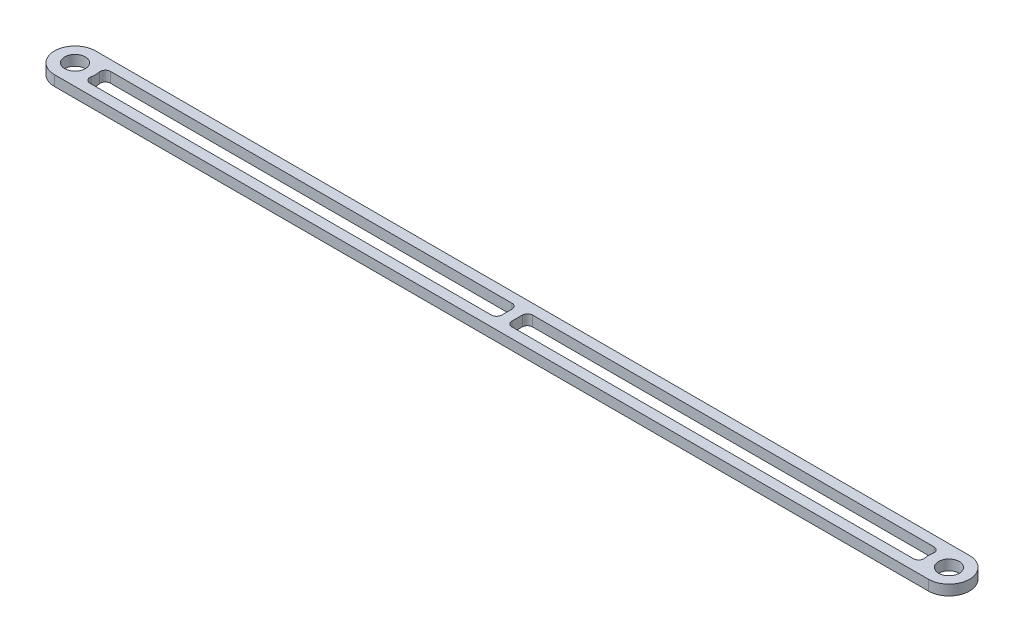
SolidWorks part; units mm, degrees
ref_plane "Front Plane" through (0, 0, 0) normal (0, 0, 1) x (1, 0, 0)
ref_plane "Top Plane" through (0, 0, 0) normal (0, 1, 0) x (1, 0, 0)
ref_plane "Right Plane" through (0, 0, 0) normal (1, 0, 0) x (0, 0, -1)
sketch "Sketch1" plane through (0, 0, 0) normal (0, 1, 0) x (1, 0, 0)
  line L0 (170, 0) -> (0, 0) construction
  line L1 (0, 4) -> (170, 4)
  line L2 (0, -4) -> (170, -4)
  line L3 (0, 2) -> (170, 2)
  line L4 (170, -2) -> (0, -2)
  line L5 (85, 2) -> (85, -2) construction
  line L6 (84, 2) -> (84, -2)
  line L7 (86, 2) -> (86, -2)
  circle A0 centre (0, 0) radius 2
  circle A1 centre (170, 0) radius 2
  circle A2 centre (0, 0) radius 4
  circle A3 centre (170, 0) radius 4
  dimension "D1" = 4
  dimension "D2" = 4
  dimension "D4" = 2
  dimension "D5" = 2
  dimension "D6" = 1
  dimension "D3" = 170
  dimension "D7" = 2
extrude "Boss-Extrude1" add sketch "Sketch1" along normal blind 2 contours A2 L4 A0 L3 | L4 A2 L3 A0 | A3 L4 A2 L2 | A3 L1 A2 L3 | L7 L3 L6 L4 | A3 L3 A1 L4 | L3 A3 L4 A1 region at (1.9453, 0, -3.3693) region at (85, 0, -3.0054) region at (172.7511, 0, -2.7511) region at (85, 0, 3.0054) region at (2.66, 0, 0) region at (167.34, 0, 0) region at (85, 0, 0)
fillet "Fillet1" radius 1 8 edges at (166.5359, 1, 2) (166.5359, 1, -2) (84, 1, 2) (86, 1, 2) (84, 1, -2) (86, 1, -2) (3.4641, 1, 2) (3.4641, 1, -2)
